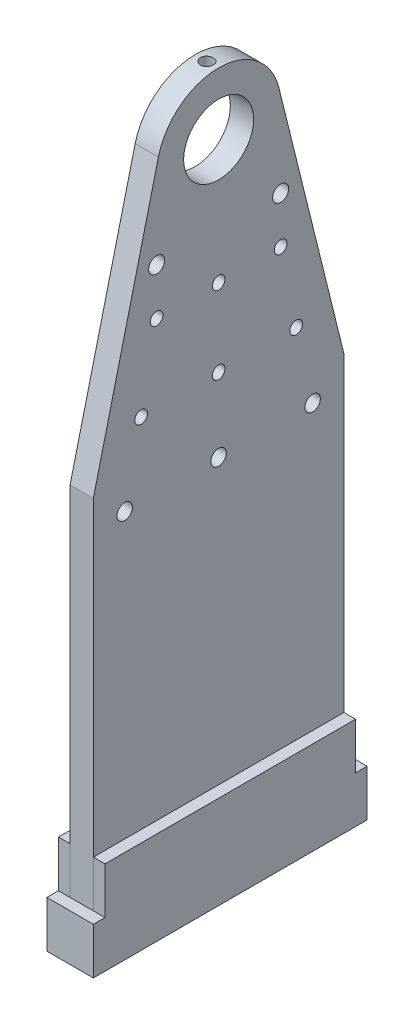
SolidWorks part; units mm, degrees
ref_plane "Front Plane" through (0, 0, 0) normal (0, 0, 1) x (1, 0, 0)
ref_plane "Top Plane" through (0, 0, 0) normal (0, 1, 0) x (1, 0, 0)
ref_plane "Right Plane" through (0, 0, 0) normal (1, 0, 0) x (0, 0, -1)
ref_plane "Plane1" through (-47.625, 0, 0) normal (1, 0, 0) x (0, 0, -1)
sketch "Sketch2" plane through (-47.625, 0, 0) normal (1, 0, 0) x (0, 0, -1)
  line L0 (-51.3017, 52.8) -> (-51.3017, 66.8)
  line L1 (51.3017, 66.8) -> (51.3017, 52.8)
  line L2 (51.3017, 66.8) -> (51.3017, 52.8) construction
  line L3 (-51.3017, 52.8) -> (-51.3017, 66.8) construction
  line L4 (51.3017, -52.8) -> (51.3017, -66.8)
  line L5 (-51.3017, -66.8) -> (-51.3017, -52.8)
  line L6 (-51.3017, -66.8) -> (-51.3017, -52.8) construction
  line L7 (51.3017, -52.8) -> (51.3017, -66.8) construction
  line L8 (0, 0) -> (0, 187.45) construction
  line L15 (51.3017, 73.15) -> (51.3017, 85.85)
  line L16 (-51.3017, -66.8) -> (51.3017, -66.8)
  line L17 (-51.3017, -66.8) -> (-51.3017, 73.15)
  line L18 (-51.3017, 73.15) -> (51.3017, 73.15) construction
  line L19 (51.3017, -66.8) -> (51.3017, 73.15)
  line L20 (51.3017, 85.85) -> (24.6566, 193.5501)
  line L21 (-51.3017, 85.85) -> (-24.6566, 193.5501)
  line L23 (-51.3017, 73.15) -> (-51.3017, 85.85)
  circle A0 centre (0, 187.45) radius 14.3129
  arc A1 (24.6566, 193.5501) -> (-24.6566, 193.5501) centre (0, 187.45) ccw
  circle A8 centre (38.4762, 74.7375) radius 3.175
  circle A9 centre (0, 74.7375) radius 3.175
  circle A10 centre (-38.4762, 74.7375) radius 3.175
  circle A11 centre (-25.4, 136.65) radius 3.175 construction
  circle A12 centre (-31.75, 104.9) radius 3.175 construction
  circle A13 centre (0, 136.65) radius 3.175 construction
  circle A14 centre (0, 104.9) radius 3.175 construction
  circle A15 centre (31.75, 104.9) radius 3.175 construction
  circle A16 centre (-25.4, 136.65) radius 3.175 construction
  circle A17 centre (-31.75, 104.9) radius 3.175 construction
  circle A18 centre (0, 136.65) radius 3.175 construction
  circle A19 centre (0, 104.9) radius 3.175 construction
  circle A20 centre (31.75, 104.9) radius 3.175 construction
  circle A21 centre (0, 136.65) radius 2.6035
  circle A22 centre (-25.4, 136.65) radius 2.6035
  circle A23 centre (-31.75, 104.9) radius 2.6035
  circle A24 centre (0, 104.9) radius 2.6035
  circle A25 centre (31.75, 104.9) radius 2.6035
  circle A26 centre (25.4, 136.65) radius 2.6035
  circle A27 centre (-25.4, 155.7) radius 3.2639
  circle A28 centre (25.4, 155.7) radius 3.2639
  circle A29 centre (38.4762, 74.7375) radius 2.6035 construction
  circle A30 centre (0, 74.7375) radius 2.6035 construction
  circle A31 centre (-38.4762, 74.7375) radius 2.6035 construction
  circle A32 centre (38.4762, 74.7375) radius 2.6035 construction
  circle A33 centre (0, 74.7375) radius 2.6035 construction
  circle A34 centre (-38.4762, 74.7375) radius 2.6035 construction
  dimension "D1" = 28.6258
  dimension "D2" = 25.4
  dimension "D6" = 6.35
  dimension "D7" = 5.207
  dimension "D8" = 6.5278
  dimension "D3" = 6.35
  dimension "D4" = 114.3
  dimension "D5" = 12.7
  dimension "D9" = 25.4
  dimension "D10" = 31.75
extrude "Boss-Extrude1" add sketch "Sketch2" along normal blind 9.525
chamfer "Chamfer1" distance 4.7625 3 edges at (-47.625, 74.7375, -3.175) (-47.625, 74.7375, -41.6512) (-47.625, 74.7375, 35.3012)
sketch "Sketch3" plane through (0, -66.8, 0) normal (0, -1, 0) x (1, 0, 0)
  line L0 (-47.625, 0) -> (-38.1, 0) construction
  line L1 (-47.625, 0) -> (-38.1, -51.3017) construction
  line L2 (-42.8625, -25.6508) -> (-42.8625, -51.3017) construction
  line L4 (-47.625, 51.3017) -> (-47.625, -51.3017)
  line L5 (-47.625, -51.3017) -> (-38.1, -51.3017)
  line L6 (-38.1, -51.3017) -> (-38.1, 51.3017)
  line L7 (-38.1, 51.3017) -> (-47.625, 51.3017)
  line L8 (-47.625, 51.3017) -> (-47.625, -51.3017) construction
  line L9 (-47.625, -51.3017) -> (-38.1, -51.3017) construction
  line L10 (-38.1, -51.3017) -> (-38.1, 51.3017) construction
  line L11 (-38.1, 51.3017) -> (-47.625, 51.3017) construction
  circle A0 centre (-42.8625, -38.4762) radius 2.6035
  circle A1 centre (-42.8625, 0) radius 2.6035
  circle A2 centre (-42.8625, 38.4762) radius 2.6035
  dimension "D2" = 5.207
  dimension "D1" = 0
extrude "Cut-Extrude1" cut sketch "Sketch3" against normal blind 25.4
ref_plane "Plane2" through (0, 212.85, 0) normal (0, 1, 0) x (-1, 0, 0)
sketch "Sketch4" plane through (0, 212.85, 0) normal (0, 1, 0) x (-1, 0, 0)
  line L4 (47.625, 0) -> (38.1, 0)
  line L5 (47.625, 0) -> (38.1, 0) construction
  circle A0 centre (42.8625, 0) radius 2.6035
  dimension "D1" = 5.207
extrude "Cut-Extrude2" cut sketch "Sketch4" against normal up to surface (11.3259 mm away) up to face at (-38.1, 187.45, -14.3129)
sketch "Sketch5" plane through (0, -66.8, 0) normal (0, -1, 0) x (1, 0, 0)
  line L0 (-42.8625, -51.3017) -> (-42.8625, 51.3017) construction
  line L1 (-38.1, 51.3017) -> (-33.3375, 51.3017)
  line L2 (-38.1, 51.3017) -> (-38.1, -51.3017)
  line L3 (-38.1, -51.3017) -> (-33.3375, -51.3017)
  line L4 (-47.625, 51.3017) -> (-47.625, -51.3017)
  line L5 (-47.625, -51.3017) -> (-38.1, -51.3017)
  line L6 (-38.1, -51.3017) -> (-38.1, 51.3017)
  line L7 (-38.1, 51.3017) -> (-47.625, 51.3017)
  line L8 (-47.625, 51.3017) -> (-47.625, -51.3017)
  line L9 (-47.625, -51.3017) -> (-38.1, -51.3017)
  line L10 (-38.1, -51.3017) -> (-38.1, 51.3017)
  line L11 (-38.1, 51.3017) -> (-47.625, 51.3017)
  line L12 (-33.3375, 51.3017) -> (-33.3375, -51.3017)
  line L13 (-47.625, -51.3017) -> (-52.3875, -51.3017)
  line L14 (-52.3875, 51.3017) -> (-52.3875, -51.3017)
  line L15 (-47.625, 51.3017) -> (-52.3875, 51.3017)
  line L16 (-47.625, 51.3017) -> (-47.625, -51.3017)
  line L17 (-42.8625, 0) -> (-38.1, 0) construction
  line L18 (-52.3875, 51.3017) -> (-33.3375, 51.3017)
  line L19 (-52.3875, 51.3017) -> (-52.3875, 56.0642)
  line L20 (-52.3875, 56.0642) -> (-33.3375, 56.0642)
  line L21 (-33.3375, 51.3017) -> (-33.3375, 56.0642)
  line L22 (-52.3875, -56.0642) -> (-33.3375, -56.0642)
  line L23 (-33.3375, -51.3017) -> (-33.3375, -56.0642)
  line L24 (-52.3875, -51.3017) -> (-33.3375, -51.3017)
  line L25 (-52.3875, -51.3017) -> (-52.3875, -56.0642)
  circle A1 centre (-42.8625, -38.4762) radius 2.6035
  circle A2 centre (-42.8625, -38.4762) radius 2.6035
  circle A3 centre (-42.8625, 0) radius 2.6035
  circle A4 centre (-42.8625, 0) radius 2.6035
  circle A5 centre (-42.8625, 38.4762) radius 2.6035
  circle A6 centre (-42.8625, 38.4762) radius 2.6035
  circle M13 centre (-42.8625, -38.4762) radius 2.6035
  circle M14 centre (-42.8625, 0) radius 2.6035
  circle M15 centre (-42.8625, 38.4762) radius 2.6035
  line M16 (-47.625, 51.3017) -> (-47.625, -51.3017)
  line M17 (-47.625, -51.3017) -> (-38.1, -51.3017)
  line M18 (-38.1, -51.3017) -> (-38.1, 51.3017)
  line M19 (-38.1, 51.3017) -> (-47.625, 51.3017)
  dimension "D5" = 4.7625
  dimension "D1" = 0
  dimension "D2" = 0
  dimension "D3" = 0
  dimension "D4" = 0
extrude "Boss-Extrude2" add sketch "Sketch5" along normal blind 12.7 separate body contours L15 L14 L13 M16 | L1 L21 L20 L19 L15 M19 | M19 M16 M17 M18 M14 M15 M13 | L12 L1 L3 M18 | L13 L25 L22 L23 L3 M17 region at (-42.8625, -66.8, 53.6829) region at (-35.7188, -66.8, 0) region at (-39.1304, -66.8, 0) region at (-42.8625, -66.8, -53.6829) region at (-50.0062, -66.8, 0)
extrude "Boss-Extrude3" add sketch "Sketch5<3>" against normal blind 25.4 contours L12 L1 L3 M18 | L15 L14 L13 M16 region at (-35.7188, -66.8, 0) region at (-50.0062, -66.8, 0)
sketch "Sketch5<3>" plane through (0, -66.8, 0) normal (0, -1, 0) x (1, 0, 0) same geometry as "Sketch5"
extrude "Boss-Extrude4" add sketch "Sketch5<4>" against normal blind 6.35 contours L1 L21 L20 L19 L15 M19 | L13 L25 L22 L23 L3 M17 region at (-42.8625, -66.8, 53.6829) region at (-42.8625, -66.8, -53.6829)
sketch "Sketch5<4>" plane through (0, -66.8, 0) normal (0, -1, 0) x (1, 0, 0) same geometry as "Sketch5"
